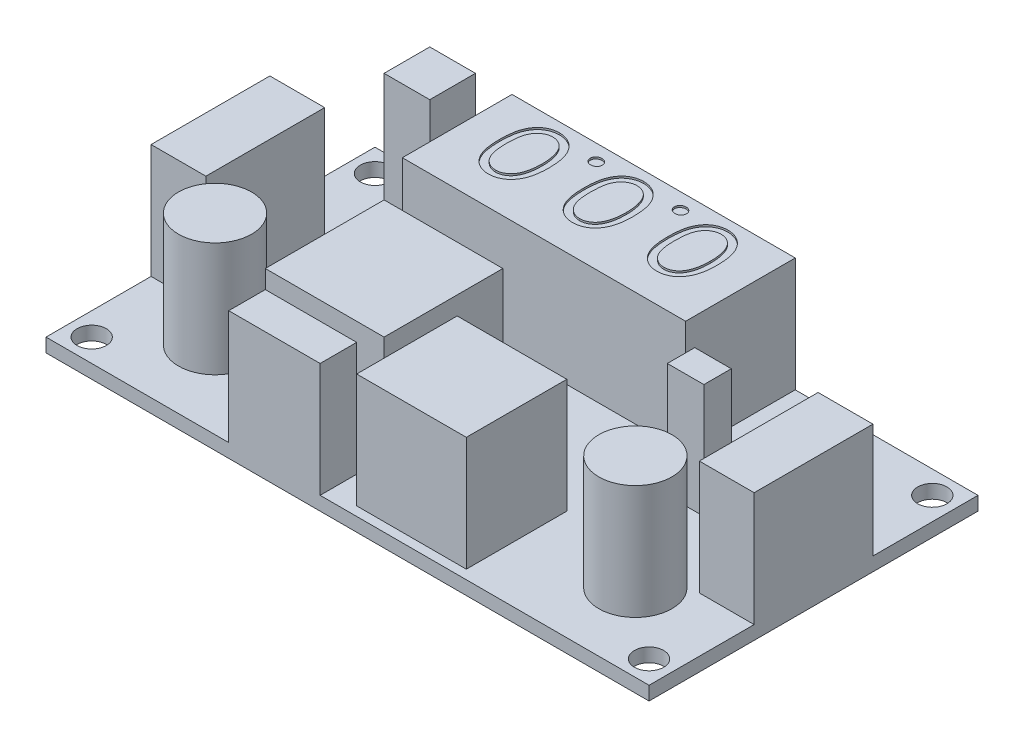
SolidWorks part; units mm, degrees
ref_plane "정면" through (0, 0, 0) normal (0, 0, 1) x (1, 0, 0)
ref_plane "윗면" through (0, 0, 0) normal (0, 1, 0) x (1, 0, 0)
ref_plane "우측면" through (0, 0, 0) normal (1, 0, 0) x (0, 0, -1)
sketch "스케치2" plane through (0, 0, 0) normal (0, 1, 0) x (1, 0, 0)
  line L1 (-33, 18) -> (33, 18)
  line L2 (-33, 18) -> (-33, -18)
  line L3 (-33, -18) -> (33, -18)
  line L4 (33, 18) -> (33, -18)
  line L5 (-33, 18) -> (33, -18) construction
  line L6 (-33, -18) -> (33, 18) construction
  point P0 (0, 0)
  dimension "D1" = 66
  dimension "D2" = 36
extrude "보스-돌출1" add sketch "스케치2" along normal blind 1.5
sketch "스케치3" plane through (0, 1.5, 0) normal (0, 1, 0) x (1, 0, 0)
  line L0 (-33, 18) -> (-33, -18) construction
  line L1 (-33, 6.5) -> (-27, 6.5)
  line L2 (-33, 6.5) -> (-33, -6.5)
  line L3 (-33, -6.5) -> (-27, -6.5)
  line L4 (-27, 6.5) -> (-27, -6.5)
  line L5 (33, -18) -> (33, 18) construction
  line L6 (33, 6.5) -> (27, 6.5)
  line L7 (33, 6.5) -> (33, -6.5)
  line L8 (33, -6.5) -> (27, -6.5)
  line L9 (27, 6.5) -> (27, -6.5)
  line L10 (-33, -18) -> (33, -18) construction
  line L11 (-13, -18) -> (-3, -18)
  line L12 (-13, -18) -> (-13, -14)
  line L13 (-13, -14) -> (-3, -14)
  line L14 (-3, -18) -> (-3, -14)
  line L15 (33, 18) -> (-33, 18) construction
  line L16 (0, -6) -> (12, -6)
  line L17 (0, -6) -> (0, -17)
  line L18 (0, -17) -> (12, -17)
  line L19 (12, -6) -> (12, -17)
  line L20 (0, -6) -> (12, -17) construction
  line L21 (0, -17) -> (12, -6) construction
  line L22 (-27, 18) -> (-22, 18)
  line L23 (-27, 18) -> (-27, 13)
  line L24 (-27, 13) -> (-22, 13)
  line L25 (-22, 18) -> (-22, 13)
  line L31 (-18, 18) -> (13, 18)
  line L32 (-18, 18) -> (-18, 6)
  line L33 (-18, 6) -> (13, 6)
  line L34 (13, 18) -> (13, 6)
  line L35 (16, 4) -> (20, 4)
  line L36 (16, 4) -> (16, 1)
  line L37 (16, 1) -> (20, 1)
  line L38 (20, 4) -> (20, 1)
  line L39 (-2, 1) -> (-15, 1)
  line L40 (-2, 1) -> (-2, -12)
  line L41 (-2, -12) -> (-15, -12)
  line L42 (-15, 1) -> (-15, -12)
  circle A0 centre (-23, -9.5) radius 4
  circle A1 centre (23, -9.5) radius 4
  point P12 (-33, 0)
  point P13 (-33, 0)
  point P27 (6, -11.5)
  dimension "D3" = 10
  dimension "D5" = 8
  dimension "D7" = 10
  dimension "D8" = 8.5
  dimension "D9" = 10
  dimension "D10" = 1
  dimension "D11" = 3
  dimension "D12" = 20
  dimension "D13" = 13
  dimension "D16" = 13
  dimension "D1" = 6
  dimension "D2" = 13
  dimension "D4" = 4
  dimension "D6" = 8.5
  dimension "D14" = 12
  dimension "D15" = 11
  dimension "D17" = 5
  dimension "D18" = 20
  dimension "D20" = 6
  dimension "D22" = 4
  dimension "D24" = 12
  dimension "D25" = 4
  dimension "D26" = 4
  dimension "D27" = 3
  dimension "D28" = 1
  dimension "D29" = 2
  dimension "D30" = 7
extrude "보스-돌출2" add sketch "스케치3" along normal blind 12.5
extrude "보스-돌출3" add sketch "스케치3<2>" along normal blind 8
sketch "스케치3<2>" plane through (0, 1.5, 0) normal (0, 1, 0) x (1, 0, 0) same geometry as "스케치3"
sketch "스케치5" plane through (0, 14, 0) normal (0, 1, 0) x (1, 0, 0)
  line L0 (-18, 16.7644) -> (13, 16.7644) construction
  line L1 (-18, 18) -> (-18, 6) construction
  line L2 (13, 6) -> (13, 18) construction
  text T0 "0.0.0" font "Century Gothic" height in points 28
  point P3 (-13.15, 8.2446)
  point P6 (13.15, 7.9465)
extrude "컷-돌출1" cut sketch "스케치5" against normal blind 0.2
sketch "스케치6" plane through (0, 1.5, 0) normal (0, 1, 0) x (1, 0, 0)
  line L0 (-27, 18) -> (-33, 18) construction
  line L1 (-30.5, -15.5) -> (30.5, -15.5) construction
  line L2 (-30.5, -15.5) -> (-30.5, 15.5) construction
  line L3 (-30.5, 15.5) -> (30.5, 15.5) construction
  line L4 (30.5, -15.5) -> (30.5, 15.5) construction
  line L5 (-33, 18) -> (-33, 6.5) construction
  line L6 (-3, -18) -> (33, -18) construction
  line L7 (33, -18) -> (33, -6.5) construction
  circle A0 centre (-30.5, 15.5) radius 1.6
  circle A1 centre (30.5, 15.5) radius 1.6
  circle A2 centre (30.5, -15.5) radius 1.6
  circle A3 centre (-30.5, -15.5) radius 1.6
  dimension "D5" = 3.2
  dimension "D1" = 2.5
  dimension "D2" = 2.5
  dimension "D3" = 2.5
  dimension "D4" = 2.5
extrude "컷-돌출2" cut sketch "스케치6" against normal through all
